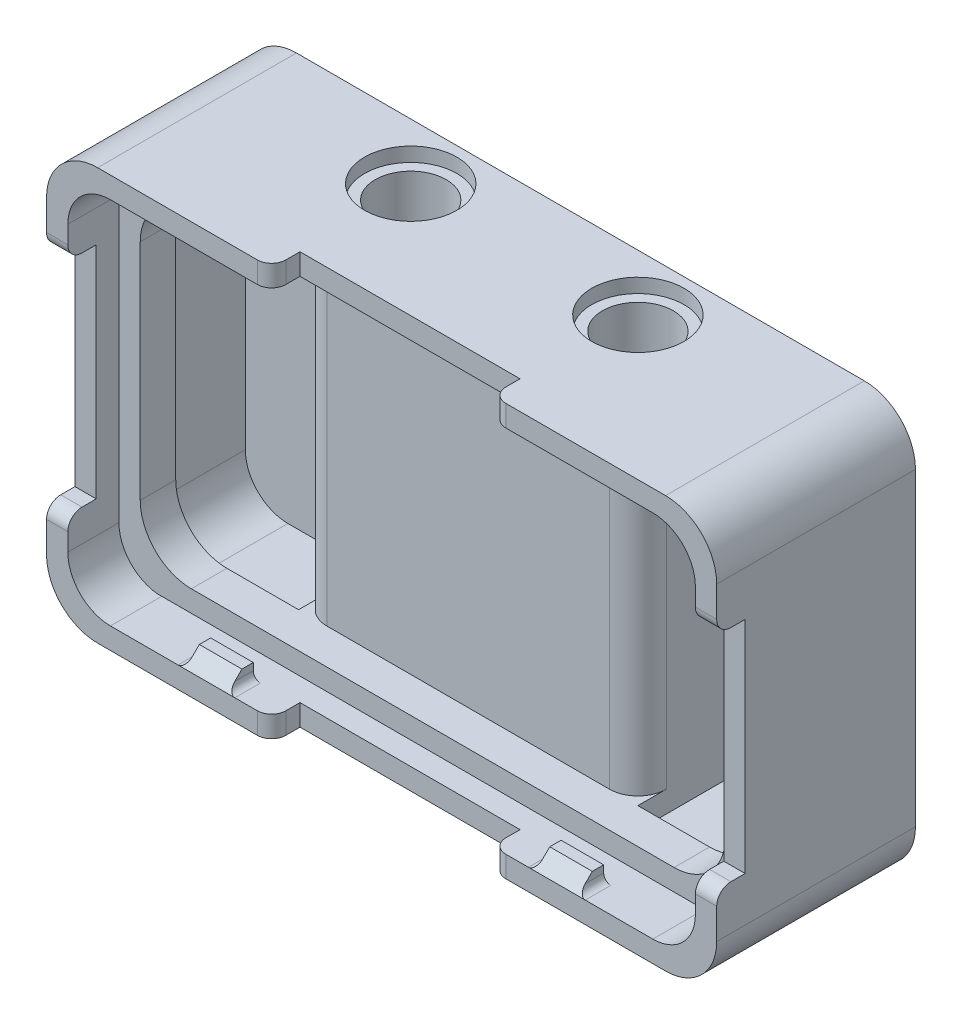
SolidWorks part; units mm, degrees
ref_plane "Front Plane" through (0, 0, 0) normal (0, 0, 1) x (1, 0, 0)
ref_plane "Top Plane" through (0, 0, 0) normal (0, 1, 0) x (1, 0, 0)
ref_plane "Right Plane" through (0, 0, 0) normal (1, 0, 0) x (0, 0, -1)
sketch "Sketch1" plane through (0, 0, 0) normal (0, 0, 1) x (1, 0, 0)
  line L0 (-22.1, -13) -> (-22.1, 13)
  line L1 (-21.6, -12.5) -> (21.6, -12.5)
  line L2 (-21.6, -12.5) -> (-21.6, 12.5)
  line L3 (-21.6, 12.5) -> (21.6, 12.5)
  line L4 (21.6, -12.5) -> (21.6, 12.5)
  line L5 (-21.6, -12.5) -> (21.6, 12.5) construction
  line L6 (-21.6, 12.5) -> (21.6, -12.5) construction
  line L7 (-22.1, 13) -> (22.1, 13)
  line L8 (22.1, -13) -> (22.1, 13)
  line L9 (-22.1, -13) -> (22.1, -13)
  line L10 (-23.6, 14.5) -> (23.6, 14.5)
  line L11 (23.6, -14.5) -> (23.6, 14.5)
  line L12 (-23.6, -14.5) -> (23.6, -14.5)
  line L13 (-23.6, -14.5) -> (-23.6, 14.5)
  point P0 (0, 0)
  dimension "D1" = 43.2
  dimension "D2" = 25
  dimension "D3" = 0.5
  dimension "D4" = 1.5
extrude "Boss-Extrude2" add sketch "Sketch1" along normal blind 14 contours L13 L12 L11 L10 L9 L0 L7 L8
sketch "Sketch2" plane through (0, 0, 0) normal (0, 0, -1) x (-1, 0, 0)
  line L1 (-22.1, 13) -> (22.1, 13)
  line L2 (-22.1, 13) -> (-22.1, -13)
  line L3 (-22.1, -13) -> (22.1, -13)
  line L4 (22.1, 13) -> (22.1, -13)
extrude "Boss-Extrude3" add sketch "Sketch2" against normal blind 1.5
sketch "Sketch3" plane through (0, -14.5, 0) normal (0, -1, 0) x (1, 0, 0)
  line L0 (0, 0) -> (0, 3.95)
  line L1 (-23.6, 0) -> (23.6, 0) construction
  line L2 (-8, 3.95) -> (8, 3.95)
  line L4 (-11.95, 7.9) -> (11.95, 7.9)
  line L5 (-11.95, 7.9) -> (-11.95, 0)
  line L6 (-11.95, 0) -> (11.95, 0)
  line L7 (11.95, 7.9) -> (11.95, 0)
  line L8 (-11.95, 7.9) -> (11.95, 0) construction
  line L9 (-11.95, 0) -> (11.95, 7.9) construction
  circle A0 centre (-8, 3.95) radius 2.45
  circle A1 centre (8, 3.95) radius 2.45
  point P7 (0, 3.95)
  dimension "D2" = 4.9
  dimension "D3" = 4.9
  dimension "D1" = 16
  dimension "D4" = 3.95
  dimension "D5" = 23.9
extrude "Boss-Extrude4" add sketch "Sketch3" against normal up to surface (29 mm away)
sketch "Sketch4" plane through (0, -14.5, 0) normal (0, -1, 0) x (1, 0, 0)
  line L0 (0, 0) -> (0, 3.95)
  line L1 (-8, 3.95) -> (8, 3.95)
  circle A0 centre (-8, 3.95) radius 2.5
  circle A1 centre (8, 3.95) radius 2.5
  point P6 (0, 3.95)
  point P8 (0, 0)
  dimension "D3" = 5
  dimension "D4" = 5
  dimension "D1" = 3.95
  dimension "D2" = 16
extrude "Cut-Extrude1" cut sketch "Sketch4" against normal up to surface (29 mm away) up to face at (0, 14.5, 7)
sketch "Sketch5" plane through (0, -14.5, 0) normal (0, -1, 0) x (1, 0, 0)
  circle A0 centre (-8, 3.95) radius 3.25
  circle A1 centre (8, 3.95) radius 3.25
  dimension "D1" = 6.5
  dimension "D2" = 6.5
extrude "Cut-Extrude2" cut sketch "Sketch5" against normal blind 1
sketch "Sketch6" plane through (0, 14.5, 0) normal (0, 1, 0) x (1, 0, 0)
  circle A0 centre (-8, -3.95) radius 3.25
  circle A1 centre (8, -3.95) radius 3.25
  dimension "D1" = 6.5
  dimension "D2" = 6.5
extrude "Cut-Extrude3" cut sketch "Sketch6" against normal blind 1
ref_plane "Plane1" through (0, 0, 0) normal (0, 1, 0) x (1, 0, 0)
sketch "Sketch8" plane through (0, 0, 0) normal (0, 1, 0) x (1, 0, 0)
  line L0 (0, 0) -> (0, -3.95)
  line L1 (-8, -3.95) -> (8, -3.95)
  circle A0 centre (-8, -3.95) radius 3.25
  circle A1 centre (8, -3.95) radius 3.25
  point P6 (0, -3.95)
  dimension "D3" = 6.5
  dimension "D4" = 6.5
  dimension "D1" = 16
  dimension "D2" = 3.95
extrude "Cut-Extrude4" cut sketch "Sketch8" against normal blind 7.5 and the other way blind 7.5 contours A0 | A1
sketch "Sketch9" plane through (0, 0, 7.9) normal (0, 0, 1) x (1, 0, 0)
  line L0 (22.1, -13) -> (22.1, 13) construction
  line L1 (-22.1, -12.9842) -> (22.1, -12.9842)
  line L2 (-22.1, -12.9842) -> (-22.1, 12.9842)
  line L3 (-22.1, 12.9842) -> (22.1, 12.9842)
  line L4 (22.1, -12.9842) -> (22.1, 12.9842)
  line L5 (-22.1, -12.9842) -> (22.1, 12.9842) construction
  line L6 (-22.1, 12.9842) -> (22.1, -12.9842) construction
  line L7 (22.1, 13) -> (22.1, -13) construction
  line L8 (-20.6, -11.4842) -> (-20.6, 11.4842)
  line L9 (-20.6, 11.4842) -> (20.6, 11.4842)
  line L10 (20.6, -11.4842) -> (20.6, 11.4842)
  line L11 (-20.6, -11.4842) -> (20.6, -11.4842)
  point P0 (0, 0)
  line M9 (-11.95, -13) -> (11.95, -13)
  line M10 (11.95, -13) -> (11.95, 13)
  line M11 (11.95, 13) -> (-11.95, 13)
  line M12 (-11.95, 13) -> (-11.95, -13)
  dimension "D1" = 1.5
extrude "Boss-Extrude5" add sketch "Sketch9" along normal blind 2.5 contours L11 L8 L9 L3 L2 L1 M12 | L9 M12 M10 M11 | L11 L1 L4 L3 L9 L10 M10 | L11 M12 M9 M10
sketch "Sketch10" plane through (0, 0, 14) normal (0, 0, 1) x (1, 0, 0)
  line L0 (0, 14.5) -> (0, 13)
  line L1 (-23.6, 14.5) -> (23.6, 14.5) construction
  line L2 (-22.1, 13) -> (22.1, 13) construction
  line L3 (23.6, 0) -> (22.1, 0)
  line L4 (23.6, -14.5) -> (23.6, 14.5) construction
  line L5 (22.1, -13) -> (22.1, 13) construction
  line L6 (-23.6, 0) -> (-22.1, 0)
  line L7 (-23.6, -14.5) -> (-23.6, 14.5) construction
  line L8 (-22.1, -13) -> (-22.1, 13) construction
  line L9 (0, -14.5) -> (0, -13)
  line L10 (-23.6, -14.5) -> (23.6, -14.5) construction
  line L11 (-22.1, -13) -> (22.1, -13) construction
  line L12 (-22.1, -12.9842) -> (-22.1, 12.9842) construction
  line L13 (-7.75, 13) -> (7.75, 13)
  line L14 (-7.75, 13) -> (-7.75, 14.5)
  line L15 (-7.75, 14.5) -> (7.75, 14.5)
  line L16 (7.75, 13) -> (7.75, 14.5)
  line L17 (-7.75, 13) -> (7.75, 14.5) construction
  line L18 (-7.75, 14.5) -> (7.75, 13) construction
  line L19 (22.1, -7.75) -> (23.6, -7.75)
  line L20 (22.1, -7.75) -> (22.1, 7.75)
  line L21 (22.1, 7.75) -> (23.6, 7.75)
  line L22 (23.6, -7.75) -> (23.6, 7.75)
  line L23 (22.1, -7.75) -> (23.6, 7.75) construction
  line L24 (22.1, 7.75) -> (23.6, -7.75) construction
  line L25 (-7.75, -14.5) -> (7.75, -14.5)
  line L26 (-7.75, -14.5) -> (-7.75, -13)
  line L27 (-7.75, -13) -> (7.75, -13)
  line L28 (7.75, -14.5) -> (7.75, -13)
  line L29 (-7.75, -14.5) -> (7.75, -13) construction
  line L30 (-7.75, -13) -> (7.75, -14.5) construction
  line L31 (-23.6, -7.75) -> (-22.1, -7.75)
  line L32 (-23.6, -7.75) -> (-23.6, 7.75)
  line L33 (-23.6, 7.75) -> (-22.1, 7.75)
  line L34 (-22.1, -7.75) -> (-22.1, 7.75)
  line L35 (-23.6, -7.75) -> (-22.1, 7.75) construction
  line L36 (-23.6, 7.75) -> (-22.1, -7.75) construction
  point P24 (0, 13.75)
  point P29 (22.85, 0)
  point P34 (0, -13.75)
  point P39 (-22.85, 0)
  dimension "D1" = 15.5
  dimension "D2" = 15.5
  dimension "D3" = 15.5
  dimension "D4" = 15.5
extrude "Cut-Extrude6" cut sketch "Sketch10" against normal blind 2 contours L33 L34 L31 L32 | L14 L15 L16 L13 | L21 L22 L19 L20 | L28 L27 L26 L25
fillet "Fillet1" radius 2 2 edges at (11.95, 0, 7.9) (-11.95, 0, 7.9)
sketch "Sketch12" plane through (0, 0, 14) normal (0, 0, 1) x (1, 0, 0)
  line L0 (-7.75, 13) -> (-12.3396, 13)
  line L8 (-22.1, 13) -> (22.1, 13) construction
  line L9 (-12.3396, 13) -> (-12.3396, 12.5)
  line L10 (0, 0) -> (-16.2349, 0)
  line L11 (-13.8396, 12) -> (-10.8396, 12)
  line L12 (-13.8396, 12) -> (-13.8396, 13)
  line L13 (-13.8396, 13) -> (-10.8396, 13)
  line L14 (-10.8396, 12) -> (-10.8396, 13)
  line L15 (-13.8396, 12) -> (-10.8396, 13) construction
  line L16 (-13.8396, 13) -> (-10.8396, 12) construction
  line L17 (3.52, 0) -> (-3.52, 0) construction
  line L18 (0, 0) -> (0, 6.5141)
  line L19 (-13.8396, -13) -> (-10.8396, -12) construction
  line L20 (-13.8396, -12) -> (-10.8396, -13) construction
  line L21 (-10.8396, -12) -> (-10.8396, -13)
  line L22 (-13.8396, -13) -> (-10.8396, -13)
  line L23 (-13.8396, -12) -> (-13.8396, -13)
  line L24 (-13.8396, -12) -> (-10.8396, -12)
  line L25 (-12.3396, -13) -> (-12.3396, -12.5)
  line L26 (-7.75, -13) -> (-12.3396, -13)
  line L27 (13.8396, -12) -> (10.8396, -13) construction
  line L28 (13.8396, -13) -> (10.8396, -12) construction
  line L29 (13.8396, 13) -> (10.8396, 12) construction
  line L30 (13.8396, 12) -> (10.8396, 13) construction
  line L31 (7.75, -13) -> (12.3396, -13)
  line L32 (12.3396, -13) -> (12.3396, -12.5)
  line L33 (13.8396, -12) -> (10.8396, -12)
  line L34 (13.8396, -12) -> (13.8396, -13)
  line L35 (13.8396, -13) -> (10.8396, -13)
  line L36 (10.8396, -12) -> (10.8396, -13)
  line L37 (10.8396, 12) -> (10.8396, 13)
  line L38 (13.8396, 13) -> (10.8396, 13)
  line L39 (13.8396, 12) -> (13.8396, 13)
  line L40 (13.8396, 12) -> (10.8396, 12)
  line L41 (12.3396, 13) -> (12.3396, 12.5)
  line L42 (7.75, 13) -> (12.3396, 13)
  dimension "D1" = 0.5
  dimension "D2" = 3
extrude "Boss-Extrude6" add sketch "Sketch12" against normal blind 1.8
sketch "Sketch13" plane through (-13.8396, 0, 0) normal (-1, 0, 0) x (0, 0, 1)
  line L0 (14, 13) -> (14, 12)
  line L1 (14, 12) -> (13, 12)
  line L2 (12.2, 12) -> (14, 12) construction
  line L3 (13, 12) -> (14, 13)
  line L4 (14, -13) -> (14, -12)
  line L5 (14, -12) -> (13, -12)
  line L6 (12.2, -12) -> (14, -12) construction
  line L7 (13, -12) -> (14, -13)
  dimension "D1" = 1
  dimension "D2" = 1
extrude "Cut-Extrude7" cut sketch "Sketch13" against normal up to surface (27.6792 mm away) up to face at (13.8396, -12.5, 13.1)
fillet "Fillet2" radius 0.5 8 edges at (10.8396, -13, 13.1) (13.8396, -13, 13.1) (-10.8396, -13, 13.1) (-13.8396, -13, 13.1) (-13.8396, 13, 13.1) (-10.8396, 13, 13.1) (13.8396, 13, 13.1) (10.8396, 13, 13.1)
fillet "Fillet3" radius 3.6 8 edges at (20.6, 11.4842, 9.15) (20.6, -11.4842, 9.15) (-20.6, -11.4842, 9.15) (-20.6, 11.4842, 9.15) (-23.6, 14.5, 7) (-23.6, -14.5, 7) (23.6, 14.5, 7) (23.6, -14.5, 7)
fillet "Fillet4" radius 1 8 edges at (-22.85, -7.75, 14) (-22.85, 7.75, 14) (-7.75, 13.75, 14) (7.75, 13.75, 14) (22.85, 7.75, 14) (22.85, -7.75, 14) (7.75, -13.75, 14) (-7.75, -13.75, 14)
fillet "Fillet5" radius 3 4 edges at (22.1, 13, 7.75) (-22.1, 13, 7.75) (-22.1, -13, 7.75) (22.1, -13, 7.75)
